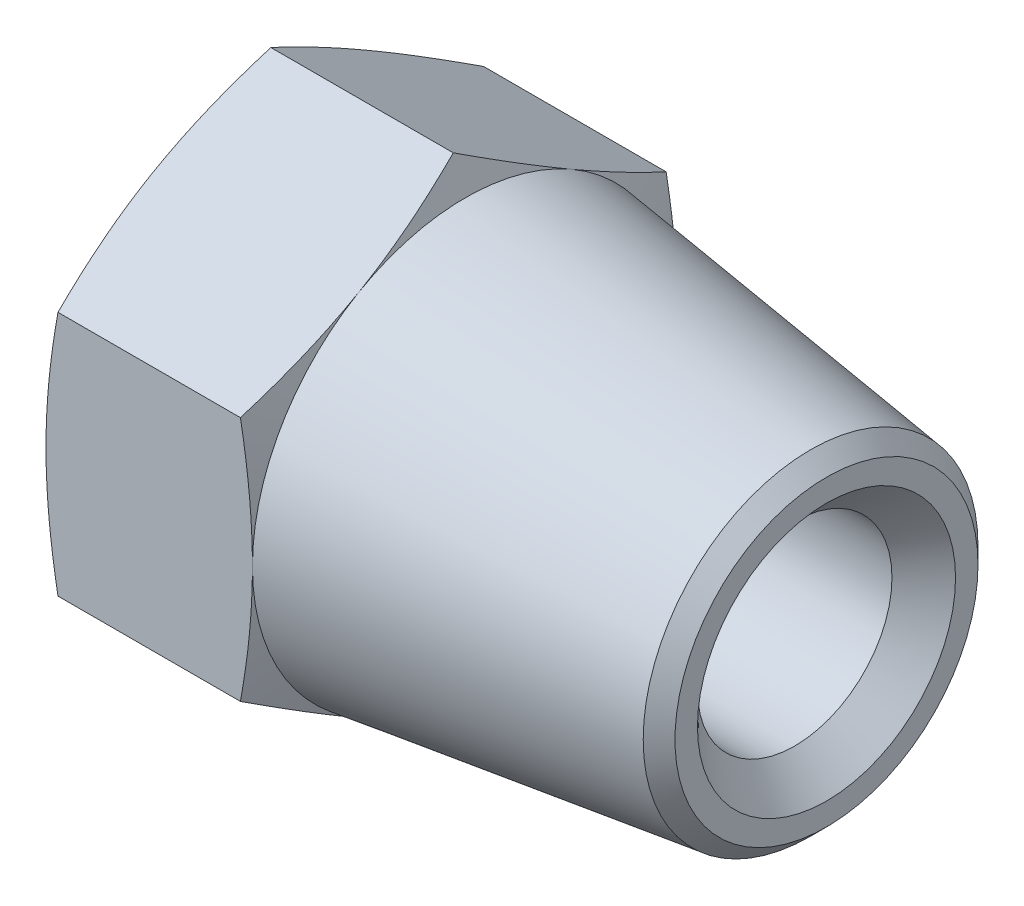
SolidWorks part; units mm, degrees
ref_plane "Front" through (0, 0, 0) normal (0, 0, 1) x (1, 0, 0)
ref_plane "Top" through (0, 0, 0) normal (0, 1, 0) x (1, 0, 0)
ref_plane "Right" through (0, 0, 0) normal (1, 0, 0) x (0, 0, -1)
sketch "Sketch1" plane through (0, 0, 0) normal (0, 0, 1) x (1, 0, 0)
  line L1 (0, 0) -> (19.05, 0) construction
  line L2 (0, 0) -> (6.35, 0)
  line L3 (0, 0) -> (0, 5.5562)
  line L4 (0, 5.5562) -> (6.35, 5.5562)
  line L5 (6.35, 0) -> (6.35, 5.5562)
  line L12 (0, 0) -> (-2.0444, 0) construction
  dimension "D1" = 6.35
  dimension "Thread Dia" = 11.1125
  dimension "L" = 19.05
revolve "Revolve1" add sketch "Sketch1" angle 360 about L12
sketch "Sketch12" plane through (0, 0, 0) normal (-1, 0, 0) x (0, 0, 1)
  circle A1 centre (0, 0) radius 5.5562
  circle A2 centre (0, 0) radius 5.5562
  dimension "D1" = 0
curve "Helix/Spiral1" pitch 1.27 height 7.62 turns 6 parameters "Pitch"=1.27
sketch "Sketch13" plane through (0, 0, 0) normal (0, 0, 1) x (1, 0, 0)
  line L0 (-1.1113, 5.5562) -> (0, 5.5562)
  line L1 (0, 5.5562) -> (-0.4763, 4.7314)
  line L2 (-0.4763, 4.7314) -> (-0.635, 4.7314)
  line L3 (-0.635, 4.7314) -> (-1.1113, 5.5562)
  line L4 (-0.5556, 4.7314) -> (-0.5556, 5.5562) construction
  line L5 (-0.8731, 5.1438) -> (-0.2381, 5.1438) construction
  dimension "D1" = 60
  dimension "D2" = 0.1588
  dimension "D3" = 0.635
sweep "Cut-Sweep1" cut profiles "Sketch13" path "Helix/Spiral1" align with end faces yes
sketch "Sketch4" plane through (0, 0, 0) normal (-1, 0, 0) x (0, 0, 1)
  line L1 (0, 8.2489) -> (-7.1438, 4.1244)
  line L2 (-7.1438, 4.1244) -> (-7.1437, -4.1244)
  line L3 (-7.1437, -4.1244) -> (0, -8.2489)
  line L4 (0, -8.2489) -> (7.1438, -4.1244)
  line L5 (7.1438, -4.1244) -> (7.1437, 4.1244)
  line L6 (7.1437, 4.1244) -> (0, 8.2489)
  circle A0 centre (0, 0) radius 7.1438 construction
  dimension "Hex" = 14.2875
extrude "Extrude1" add sketch "Sketch4" against normal blind 6.9273 separate body
combine bodies "Combine1" operation type subtract main body 150 bodies to subtract 159
sketch "Sketch9" plane through (0, 0, 0) normal (-1, 0, 0) x (0, 0, 1)
  circle A0 centre (0, 0) radius 5.5562
extrude "Cut-Extrude1" cut sketch "Sketch9" against normal through all draft 45
sketch "Sketch10" plane through (0, 0, 0) normal (-1, 0, 0) x (0, 0, 1)
  circle A0 centre (0, 0) radius 7.1438 construction
  circle A1 centre (0, 0) radius 7.1438
extrude "Cut-Extrude2" cut sketch "Sketch10" against normal through all draft 70 flip side to cut
sketch "Sketch11" plane through (6.9273, 0, 0) normal (1, 0, 0) x (0, 0, -1)
  circle A0 centre (0, 0) radius 7.1438 construction
  circle A1 centre (0, 0) radius 7.1438
extrude "Cut-Extrude3" cut sketch "Sketch11" against normal through all draft 70 flip side to cut
sketch "Sketch5" plane through (0, 0, 0) normal (0, 0, 1) x (1, 0, 0)
  line L0 (6.9273, 7.1438) -> (6.9273, 3.2639)
  line L1 (6.9273, 8.2489) -> (6.9273, 4.1244) construction
  line L2 (6.9273, 3.2639) -> (17.9834, 3.2639)
  line L3 (17.9834, 3.2639) -> (19.05, 4.3305)
  line L4 (19.05, 4.3305) -> (19.05, 5.0847)
  line L5 (19.05, 5.0847) -> (18.5167, 5.618)
  line L6 (18.5167, 5.618) -> (6.9273, 7.1438)
  line L7 (0, 7.1438) -> (6.9273, 7.1438) construction
  line L8 (0, 7.1438) -> (0, -7.1438) construction
  line L9 (0, 4.1244) -> (0, 8.2489) construction
  line L11 (19.05, 0) -> (0, 0) construction
  point P5 (18.5167, 3.7972)
  dimension "D1" = 45
  dimension "D" = 6.5278
  dimension "D2" = 7.5
revolve "Revolve2" add sketch "Sketch5" angle 360 about L11
sketch "Sketch7" plane through (0, 0, 0) normal (0, 0, 1) x (1, 0, 0)
  line L0 (11.9063, 0) -> (6.35, 5.5562)
  line L1 (6.35, 5.5562) -> (6.35, 0)
  line L2 (6.35, 0) -> (11.9063, 0)
  line L3 (0, 0) -> (19.05, 0) construction
  dimension "D1" = 45
revolve "Cut-Revolve3" cut sketch "Sketch7" angle 360 about L1
equation "\"D1@Sketch1\" = \"L@Sketch1\"/3"
equation "\"D1@Extrude1\" = \"L@Sketch1\"/2.75"
equation "\"D3@Helix/Spiral1\" = \"D1@Sketch1\"+\"Pitch@Helix/Spiral1\""
equation "\"D2@Sketch13\" = \"Pitch@Helix/Spiral1\"*.125"
equation "\"D3@Sketch13\" = \"Pitch@Helix/Spiral1\"*.50"
